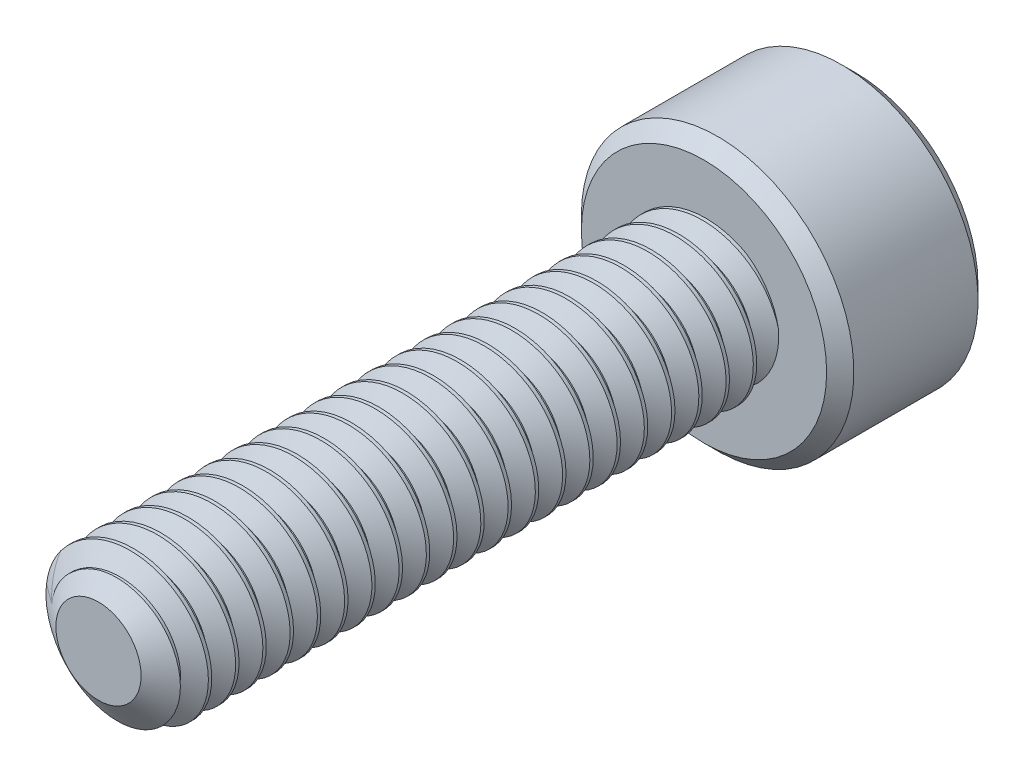
SolidWorks part; units mm, degrees
other "DetailItem1"
material "AISI Type 316L stainless steel"
ref_plane "Front Plane" through (0, 0, 0) normal (0, 0, 1) x (1, 0, 0)
ref_plane "Top Plane" through (0, 0, 0) normal (0, 1, 0) x (1, 0, 0)
ref_plane "Right Plane" through (0, 0, 0) normal (1, 0, 0) x (0, 0, -1)
sketch "Sketch1" plane through (0, 0, 0) normal (0, 0, 1) x (1, 0, 0)
  circle A0 centre (0, 0) radius 1.25
  dimension "OD" = 2.5
extrude "Extrude1" add sketch "Sketch1" against normal blind 10
sketch "Sketch2" plane through (0, 0, 0) normal (0, 0, 1) x (1, 0, 0)
  circle A0 centre (0, 0) radius 1.25 construction
  circle A1 centre (0, 0) radius 1.25
curve "Helix/Spiral1" pitch 0.45 height 10.45 radius 1.25 centre (0, 0, 0) axis (0, 0, -1) start towards (0, 1, 0) parameters "pitch"=0.45
sketch "Sketch3" plane through (0, 0, 0) normal (1, 0, 0) x (0, 0, -1)
  line L0 (-0.3938, 1.25) -> (-0.225, 0.9577)
  line L1 (-0.225, 0.9577) -> (-0.1688, 0.9577)
  line L2 (-0.1688, 0.9577) -> (0, 1.25)
  line L3 (-0.3938, 1.25) -> (0, 1.25)
  line L4 (-0.1969, 1.25) -> (-0.1969, 0.9577) construction
  line L5 (-0.3094, 1.1039) -> (-0.0844, 1.1039) construction
  line L6 (0, 1.25) -> (0, -1.25) construction
  dimension "D1" = 0.0563
  dimension "D2" = 0.225
  dimension "D3" = 60
sweep "Cut-Sweep1" cut profiles "Sketch3" path "Helix/Spiral1" align with end faces yes
sketch "Sketch4" plane through (0, 0, 0) normal (1, 0, 0) x (0, 0, -1)
  line L0 (0.3825, 1.25) -> (0, 0.7037)
  line L1 (0, 0.7037) -> (0, 1.25)
  line L2 (0.3825, 1.25) -> (0, 1.25)
  line L3 (-0.3938, 1.25) -> (0, 1.25) construction
  line L4 (0, 0) -> (7.0209, 0) construction
  dimension "D1" = 55
  dimension "D2" = 0.254
revolve "Cut-Revolve1" cut sketch "Sketch4" angle 360 about L4
sketch "Sketch6" plane through (0, 0, -10) normal (0, 0, -1) x (-1, 0, 0)
  circle A0 centre (0, 0) radius 2.25
  dimension "head dia" = 4.5
extrude "Extrude2" add sketch "Sketch6" along normal blind 2.5
sketch "Sketch7" plane through (0, 0, -12.5) normal (0, 0, -1) x (-1, 0, 0)
  line L1 (0, 1.1547) -> (-1, 0.5774)
  line L2 (-1, 0.5774) -> (-1, -0.5774)
  line L3 (-1, -0.5774) -> (0, -1.1547)
  line L4 (0, -1.1547) -> (1, -0.5774)
  line L5 (1, -0.5774) -> (1, 0.5774)
  line L6 (1, 0.5774) -> (0, 1.1547)
  circle A0 centre (0, 0) radius 1 construction
  dimension "hex dia" = 2
extrude "Cut-Extrude1" cut sketch "Sketch7" against normal blind 1.5
sketch "Sketch8" plane through (0, 0, -12.5) normal (0, 0, -1) x (-1, 0, 0)
  circle A0 centre (0, 0) radius 1.1547
extrude "Cut-Extrude2" cut sketch "Sketch8" against normal through all draft 45
chamfer "Chamfer1" distance 0.225 angle 45 2 edges at (-2.25, 0, -12.5) (-2.25, 0, -10)
sketch "Sketch10" plane through (0, 0, -10) normal (0, 0, 1) x (1, 0, 0)
  circle A1 centre (0, 0) radius 1.25
  circle A2 centre (0, 0) radius 1.25
  dimension "D1" = 0
ref_plane "Plane1" through (0, 0, 0) normal (0, 0, 1) x (1, 0, 0)
extrude "partial thread" [suppressed] add sketch "Sketch10" along normal up to surface (36 mm away) separate body up to plane "Plane1"
chamfer "Chamfer2" [suppressed] distance 0.05 angle 45
combine bodies "Combine1" [suppressed] operation type add bodies to combine 107 108
sketch "Sketch9" plane through (0, 0, 0) normal (1, 0, 0) x (0, 0, -1)
  line L0 (0, 1.25) -> (0, -1.25) construction
  line L1 (1.125, 1.25) -> (1.125, -1.25) construction
  dimension "D1" = 1.125
equation "\"D3@Helix/Spiral1\" = \"screw length@Extrude1\"+\"pitch@Helix/Spiral1\""
equation "\"D1@Sketch3\" = \"pitch@Helix/Spiral1\"*.125"
equation "\"D2@Sketch3\" = \"pitch@Helix/Spiral1\"*.5"
equation "\"D1@Cut-Extrude1\" = \"hex dia@Sketch7\"*.75"
equation "\"D1@Chamfer1\" = \"head dia@Sketch6\"*.05"
equation "\"D1@Sketch9\" = \"pitch@Helix/Spiral1\"*2.5"
equation "\"D1@Chamfer2\"=\"OD@Sketch1\"*.02"
